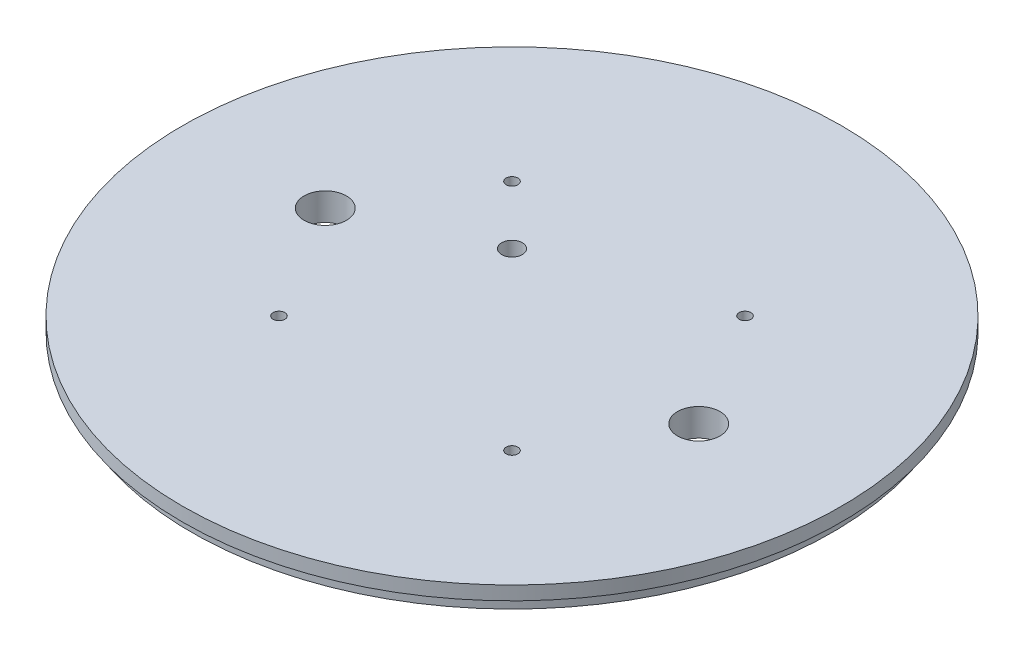
SolidWorks part; units mm, degrees
material "6061-T6 (SS)"
ref_plane "Front Plane" through (0, 0, 0) normal (0, 0, 1) x (1, 0, 0)
ref_plane "Top Plane" through (0, 0, 0) normal (0, 1, 0) x (1, 0, 0)
ref_plane "Right Plane" through (0, 0, 0) normal (1, 0, 0) x (0, 0, -1)
sketch "Sketch1" plane through (0, 0, 0) normal (0, 1, 0) x (1, 0, 0)
  line L0 (0, -76.2) -> (0, 76.2) construction
  line L1 (-76.2, 0) -> (76.2, 0) construction
  line L2 (-26.9408, 26.9408) -> (0, 0) construction
  line L3 (0, 56.7387) -> (0, 29.6936) construction
  line L4 (3.6407, 56.7387) -> (3.6407, 29.6936) construction
  line L5 (-3.6407, 56.7387) -> (-3.6407, 29.6936) construction
  line L6 (0, -56.7387) -> (0, -29.6936) construction
  line L7 (3.6407, -56.7387) -> (3.6407, -29.6936) construction
  line L8 (-3.6407, -56.7387) -> (-3.6407, -29.6936) construction
  line L9 (-53.8815, -53.8815) -> (54.3236, 54.3236) construction
  circle A0 centre (0, 0) radius 76.2
  circle A1 centre (0, 0) radius 3.175 construction
  circle A2 centre (43.18, 0) radius 4.9022
  circle A3 centre (-43.18, 0) radius 4.9022
  circle A4 centre (-26.9408, 26.9408) radius 1.3589
  arc A6 (3.6407, 56.7387) -> (-3.6407, 56.7387) centre (0, 56.7387) ccw construction
  arc A7 (-3.6407, 29.6936) -> (3.6407, 29.6936) centre (0, 29.6936) ccw construction
  arc A8 (3.6407, -56.7387) -> (-3.6407, -56.7387) centre (0, -56.7387) cw construction
  arc A9 (-3.6407, -29.6936) -> (3.6407, -29.6936) centre (0, -29.6936) cw construction
  circle A10 centre (26.9408, -26.9408) radius 1.3589
  circle A11 centre (-13.4704, 13.4704) radius 2.3813
  circle A12 centre (-26.9408, -26.9408) radius 1.3589
  circle A13 centre (26.9408, 26.9408) radius 1.3589
  circle A14 centre (-26.9408, 26.9408) radius 1.3589
  circle A15 centre (26.9408, -26.9408) radius 1.3589
  circle A16 centre (26.9408, 26.9408) radius 1.3589
  circle A17 centre (-26.9408, -26.9408) radius 1.3589
  point P16 (0, 43.2162)
  point P19 (0, 0)
  point P26 (0, -43.2162)
  point P50 (0, 0)
  dimension "D1" = 152.4
  dimension "D2" = 6.35
  dimension "D3" = 9.8044
  dimension "D5" = 2.7178
  dimension "D8" = 4.7625
  dimension "D6" = 38.1
  dimension "D7" = 45
  dimension "D4" = 45
  dimension "D9" = 43.18
  dimension "D10" = 4
extrude "Boss-Extrude1" add sketch "Sketch1" along normal blind 6.35 contours A0 A13 A10 A4 A2 A3 A11 A12 region at (0.0133, 0, 0.0133)
sketch "Sketch2" plane through (0, 0, 0) normal (0, -1, 0) x (1, 0, 0)
  circle A0 centre (0, 0) radius 76.2
  circle A1 centre (0, 0) radius 74.041
  dimension "D1" = 152.4
  dimension "D2" = 148.082
extrude "Cut-Extrude1" cut sketch "Sketch2" against normal blind 3.175
sketch "Sketch3" plane through (0, 6.35, 0) normal (0, 1, 0) x (1, 0, 0)
  line L0 (0, 76.2) -> (0, -76.2) construction
  line L1 (-76.2, 0) -> (76.2, 0) construction
  line L2 (0, 34.798) -> (0, 13.97) construction
  line L3 (3.2385, 34.798) -> (3.2385, 13.97)
  line L4 (-3.2385, 34.798) -> (-3.2385, 13.97)
  line L5 (0, -34.798) -> (0, -13.97) construction
  line L6 (3.2385, -34.798) -> (3.2385, -13.97)
  line L7 (-3.2385, -34.798) -> (-3.2385, -13.97)
  arc A1 (3.2385, 34.798) -> (-3.2385, 34.798) centre (0, 34.798) ccw
  arc A2 (-3.2385, 13.97) -> (3.2385, 13.97) centre (0, 13.97) ccw
  arc A3 (3.2385, -34.798) -> (-3.2385, -34.798) centre (0, -34.798) cw
  arc A4 (-3.2385, -13.97) -> (3.2385, -13.97) centre (0, -13.97) cw
  point P7 (0, 13.97)
  point P8 (0, 34.798)
  point P12 (0, 24.384)
  point P20 (0, -24.384)
  point P25 (0, -34.798)
  point P26 (0, -13.97)
  dimension "D1" = 13.97
  dimension "D2" = 20.828
  dimension "D3" = 6.477
extrude "Cut-Extrude2" cut sketch "Sketch3" against normal blind 3.556 from offset 3.175 offset against normal yes
equation "\"leadDist\"=1.5"
equation "\"Lead_Screw_Dist\" = 3.4in"
equation "\"Lead_Screw_Diam\" = 0.386in"
equation "\"D3@Sketch1\"=\"Lead_Screw_Diam\""
equation "\"D9@Sketch1\"=\"Lead_Screw_Dist\"/2"
